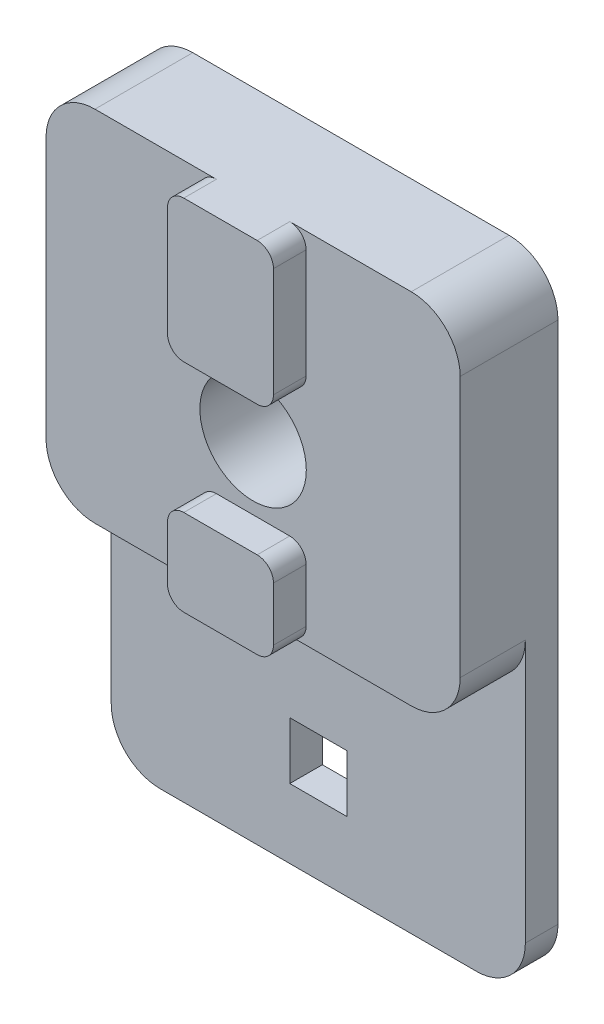
SolidWorks part; units mm, degrees
note: The reader was unsure of these and kept them because the rebuilt part matched: shared geometry of "Sketch1<3>", "main_features_sketch<4>".
ref_plane "Front Plane" through (0, 0, 0) normal (0, 0, 1) x (1, 0, 0)
ref_plane "Top Plane" through (0, 0, 0) normal (0, 1, 0) x (1, 0, 0)
ref_plane "Right Plane" through (0, 0, 0) normal (1, 0, 0) x (0, 0, -1)
sketch "main_features_sketch" plane through (0, 0, 0) normal (0, 0, 1) x (1, 0, 0)
  line L0 (0, 19.4) -> (0, 32.1) construction
  line L1 (1.75, 1.75) -> (-1.75, 1.75)
  line L2 (1.75, 1.75) -> (1.75, -1.75)
  line L3 (1.75, -1.75) -> (-1.75, -1.75)
  line L4 (-1.75, 1.75) -> (-1.75, -1.75)
  line L5 (0, -1.75) -> (0, 1.75) construction
  line L6 (1.75, 0) -> (-1.75, 0) construction
  line L11 (-12.7, 32.1) -> (12.7, 32.1)
  line L12 (-12.7, 32.1) -> (-12.7, -6)
  line L13 (-12.7, -6) -> (12.7, -6)
  line L14 (12.7, 32.1) -> (12.7, -6)
  line L15 (-12.7, 32.1) -> (12.7, -6) construction
  line L16 (-12.7, -6) -> (12.7, 32.1) construction
  line L17 (0, 19.4) -> (-12.7, 19.4) construction
  line L18 (-12.7, 10.1) -> (12.7, 10.1)
  line L20 (3.25, 10.1) -> (-3.25, 10.1)
  line L21 (3.25, 10.1) -> (3.25, 32.1)
  line L22 (3.25, 32.1) -> (-3.25, 32.1)
  line L23 (-3.25, 10.1) -> (-3.25, 32.1)
  line L24 (3.25, 10.1) -> (-3.25, 32.1) construction
  line L25 (3.25, 32.1) -> (-3.25, 10.1) construction
  line L26 (3.25, 23.4) -> (-3.25, 23.4)
  line L27 (3.25, 23.4) -> (3.25, 15.4)
  line L28 (3.25, 15.4) -> (-3.25, 15.4)
  line L29 (-3.25, 23.4) -> (-3.25, 15.4)
  line L30 (3.25, 23.4) -> (-3.25, 15.4) construction
  line L31 (3.25, 15.4) -> (-3.25, 23.4) construction
  circle A0 centre (0, 19.4) radius 3.2639
  circle A1 centre (0, 19.4) radius 7.112 construction
  point P0 (0, 0)
  point P4 (0, 0)
  point P5 (0, 13.05)
  point P17 (0, 21.1)
  dimension "D4" = 6.5278
  dimension "D5" = 14.224
  dimension "D1" = 3.5
  dimension "D2" = 25.4
  dimension "D3" = 38.1
  dimension "D6" = 6
  dimension "D7" = 22
  dimension "D8" = 6.5
  dimension "D9" = 8
extrude "base" add sketch "main_features_sketch" along normal blind 2 contours L18 L12 L13 L14 L4 L1 L2 L3 | A0 L23 L11 L12 L18 | A0 L23 L18 L21 | A0 L21 L18 L14 L11 | A0 L21 L11 L23 | A0 L23 L28 L21 | A0 L21 L26 L23
extrude "standoff" add sketch "Sketch1<3>" along normal blind 6 contours L12 L18 L14 L11 A0 | A0 L23 L11 L12 L18 | A0 L23 L18 L21 | A0 L21 L18 L14 L11 | A0 L23 L28 L21 | L26 L21 L11 L23
sketch "Sketch1<3>" plane through (0, 0, 0) normal (0, 0, 1) x (1, 0, 0) same geometry as "main_features_sketch"
extrude "pegs" add sketch "main_features_sketch<4>" along normal blind 2 from surface at 6 contours A0 L21 L11 L23 | A0 L23 L18 L21
sketch "main_features_sketch<4>" plane through (0, 0, 0) normal (0, 0, 1) x (1, 0, 0) same geometry as "main_features_sketch"
fillet "Fillet1" radius 3 6 edges at (-12.7, 10.1, 4) (12.7, 10.1, 4) (12.7, 32.1, 3) (-12.7, 32.1, 3) (-12.7, -6, 1) (12.7, -6, 1)
fillet "Fillet2" radius 1 8 edges at (3.25, 32.1, 7) (-3.25, 32.1, 7) (-3.25, 23.4, 7) (3.25, 23.4, 7) (3.25, 15.4, 7) (-3.25, 15.4, 7) (3.25, 10.1, 7) (-3.25, 10.1, 7)
